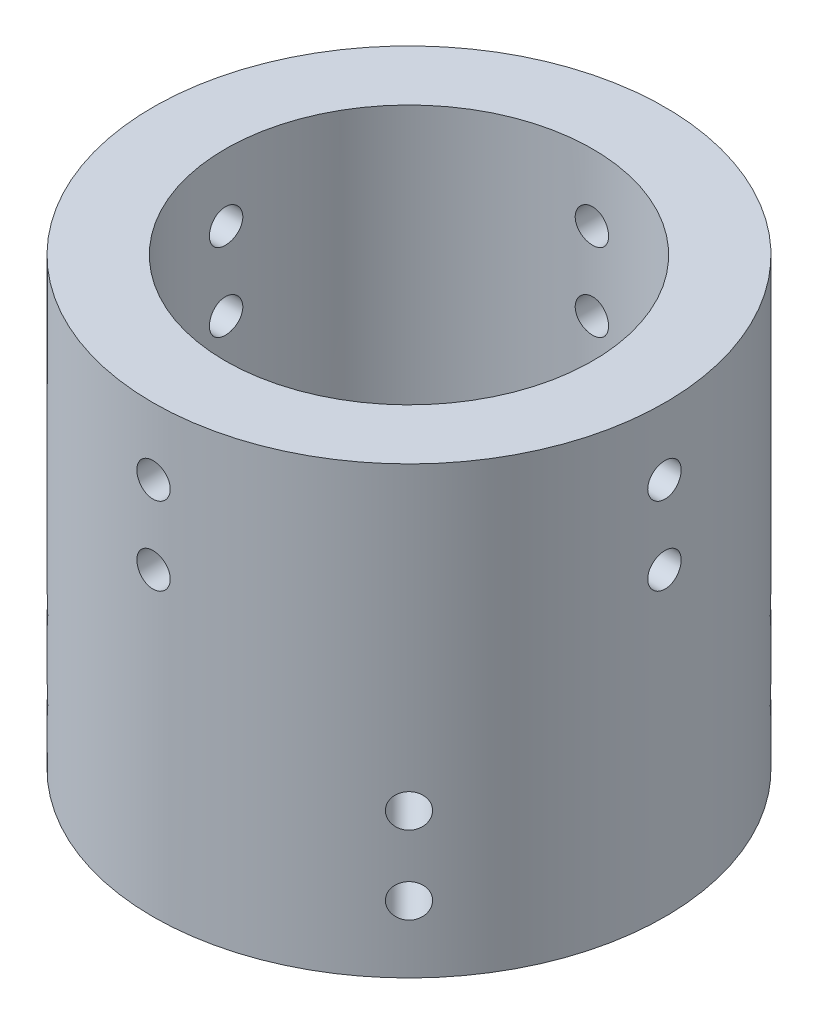
SolidWorks part; units mm, degrees
ref_plane "Спереди" through (0, 0, 0) normal (0, 0, 1) x (1, 0, 0)
ref_plane "Сверху" through (0, 0, 0) normal (0, 1, 0) x (1, 0, 0)
ref_plane "Справа" through (0, 0, 0) normal (1, 0, 0) x (0, 0, -1)
sketch "Эскиз1" plane through (0, 0, 0) normal (0, 1, 0) x (1, 0, 0)
  circle A0 centre (0, 0) radius 23
  dimension "D1" = 46
extrude "Бобышка-Вытянуть1" add sketch "Эскиз1" along normal blind 5
sketch "Эскиз2" plane through (0, 5, 0) normal (0, 1, 0) x (1, 0, 0)
  circle A0 centre (0, 0) radius 23
  circle A1 centre (0, 0) radius 16.5
  circle A2 centre (0, 0) radius 23 construction
  dimension "D1" = 33
  dimension "D2" = 0
extrude "Бобышка-Вытянуть2" add sketch "Эскиз2" along normal blind 35
sketch "Эскиз3" plane through (0, 0, 0) normal (1, 0, 0) x (0, 0, -1)
  line L0 (-23, 20) -> (28.0263, 20) construction
  line L1 (-23, 40) -> (-23, 0) construction
  circle A0 centre (0, 27) radius 1.5
  circle A1 centre (0, 34) radius 1.5
  dimension "D1" = 3
  dimension "D3" = 2
  dimension "D2" = 7
extrude "Вырез-Вытянуть1" cut sketch "Эскиз3" against normal through all
ref_plane "Плоскость1" through (0, 0, 0) normal (0.7071, 0, 0.7071) x (0, -1, 0)
sketch "Эскиз4" plane through (0, 0, 0) normal (0.7071, 0, 0.7071) x (0, -1, 0)
  line L0 (-20, 23) -> (-20, -30.0625) construction
  line L1 (0, 23) -> (-40, 23) construction
  line L2 (-40, 0) -> (0, 0) construction
  circle A0 centre (-13, 0) radius 1.5
  circle A1 centre (-6, 0) radius 1.5
  dimension "D1" = 3
  dimension "D2" = 7
  dimension "D3" = 2
extrude "Вырез-Вытянуть2" cut sketch "Эскиз4" against normal through all
pattern_circular "Круговой массив1" count 4 over 360 about axis through (0, 5, 0) along (0, -1, 0) of "Вырез-Вытянуть2", "Вырез-Вытянуть1"
